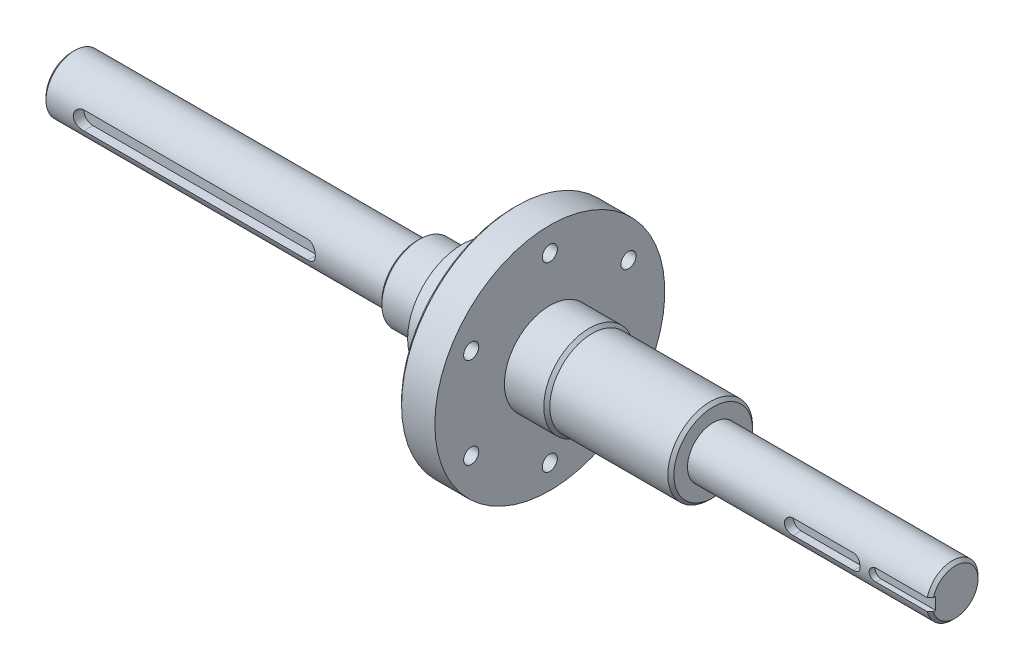
SolidWorks part; units mm, degrees
other "Element opisowy1"
other "Folder spoin"
other "Ścieg spoiny1"
material "40HMT"
ref_plane "Płaszczyzna przednia" through (0, 0, 0) normal (0, 0, 1) x (1, 0, 0)
ref_plane "Płaszczyzna górna" through (0, 0, 0) normal (0, 1, 0) x (1, 0, 0)
ref_plane "Płaszczyzna prawa" through (0, 0, 0) normal (1, 0, 0) x (0, 0, -1)
sketch "Szkic1" plane through (0, 0, 0) normal (0, 0, 1) x (1, 0, 0)
  line L0 (0, 0) -> (292, 0) construction
  line L1 (0, 0) -> (0, 9.5)
  line L2 (0, 9.5) -> (114, 9.5)
  line L3 (114, 9.5) -> (114, 12.5)
  line L4 (114, 12.5) -> (129, 12.5)
  line L5 (129, 12.5) -> (129, 18)
  line L6 (146, 38) -> (158, 38) construction
  line L7 (158, 38) -> (158, 15) construction
  line L8 (158, 15) -> (172, 15)
  line L9 (129, 18) -> (146, 18)
  line L10 (146, 18) -> (146, 38) construction
  line L11 (212, 14) -> (212, 8.5)
  line L12 (212, 8.5) -> (292, 8.5)
  line L13 (146, 18) -> (146, 15)
  line L14 (146, 15) -> (158, 15)
  line L15 (292, 8.5) -> (292, 0)
  line L16 (0, 0) -> (292, 0)
  line L17 (212, 14) -> (172, 14)
  line L18 (172, 14) -> (172, 15)
  dimension "D1" = 19
  dimension "D2" = 114
  dimension "D3" = 25
  dimension "D4" = 38
  dimension "D5" = 36
  dimension "D6" = 129
  dimension "D7" = 30
  dimension "D8" = 66
  dimension "D9" = 12
  dimension "D10" = 29
  dimension "D11" = 17
  dimension "D12" = 80
  dimension "D13" = 14
  dimension "D14" = 1
revolve "Obrót1" add sketch "Szkic1" angle 360 about L16
cosmetic thread "Oznaczenie gwintu1" parameters "D1"=20, "D2"=16
ref_plane "Płaszczyzna1" through (0, 0, 9.5) normal (0, 0, 1) x (1, 0, 0)
sketch "Szkic2" plane through (0, 0, 9.5) normal (0, 0, 1) x (1, 0, 0)
  line L0 (13, 0) -> (87, 0) construction
  line L1 (13, 3) -> (87, 3)
  line L2 (13, -3) -> (87, -3)
  line L8 (0, 9.5) -> (0, -9.5) construction
  arc A0 (13, 3) -> (13, -3) centre (13, 0) ccw
  arc A1 (87, -3) -> (87, 3) centre (87, 0) ccw
  point P3 (50, 0)
  dimension "D2" = 90
  dimension "D3" = 10
  dimension "D1" = 6
extrude "Wytnij-wyciągnięcie1" cut sketch "Szkic2" against normal blind 3.5
hole_wizard "Otwór gwintowany M61" positions "Szkic3" profile "Szkic5" tap size "M6" standard "DIN"
sketch "Szkic3" plane through (0, 0, 0) normal (-1, 0, 0) x (0, 0, 1)
  point P0 (0, 0)
sketch "Szkic5" plane through (0, 0, 0) normal (0, 1, 0) x (0, 0, 1)
  line L0 (0, 0) -> (0, 18.5022)
  line L1 (0, 18.5022) -> (2.5, 17)
  line L2 (2.5, 17) -> (2.5, 0)
  line L5 (2.5, 0) -> (0, 0)
  line L10 (0, 18.5022) -> (-2.5, 17) construction
  line L11 (0, -6.35) -> (0, 107.95) construction
  dimension "Średnica wiertła gwintu" = 5
  dimension "Głębokość otworu gwintowanego" = 17
  dimension "Kąt wiertła" = 118
cosmetic thread "Gwint otworu1" parameters "D1"=12, "D2"=6
chamfer "Sfazowanie1" distance 1 angle 45 1 edges at (0, 0, 9.5)
sketch "Szkic6" plane through (0, 0, 0) normal (0, 0, 1) x (1, 0, 0)
  line L0 (0, 0) -> (292, 0) construction
  line L2 (146, 38) -> (158, 38)
  line L3 (146, 38) -> (146, 15)
  line L4 (146, 15) -> (158, 15)
  line L5 (158, 38) -> (158, 15)
revolve "Obrót2" add sketch "Szkic6" angle 360 about L0
hole_wizard "Otwór gwintowany M62" positions "Szkic7" profile "Szkic8" tap size "M6" standard "DIN" end condition up to next
sketch "Szkic7" plane through (158, 0, 0) normal (1, 0, 0) x (0, 0, -1)
  line L0 (0, 0) -> (0, 30) construction
  point P0 (0, 30)
  dimension "D1" = 30
sketch "Szkic8" plane through (158, 30, 0) normal (0, 1, 0) x (0, 0, -1)
  line L0 (0, 0) -> (0, 12.001)
  line L1 (0, 12.001) -> (2.5, 12.001)
  line L2 (2.5, 12.001) -> (2.5, 0)
  line L5 (2.5, 0) -> (0, 0)
  line L11 (0, -6.35) -> (0, 107.95) construction
  dimension "Średnica otworu gwintowanego na wylot" = 5
  dimension "Głębokość otworu gwintowanego na wylot" = 12.001
cosmetic thread "Gwint otworu2" parameters "D2"=6
pattern_circular "Szyk kołowy1" count 6 over 360 about axis through (0, 0, 0) along (-1, 0, 0) of "Otwór gwintowany M62"
ref_plane "Płaszczyzna2" through (0, 0, 8.5) normal (0, 0, 1) x (1, 0, 0)
sketch "Szkic9" plane through (0, 0, 8.5) normal (0, 0, 1) x (1, 0, 0)
  line L0 (246.5, 0) -> (266.5, 0) construction
  line L1 (246.5, 2.5) -> (266.5, 2.5)
  line L2 (246.5, -2.5) -> (266.5, -2.5)
  line L10 (212, -8.5) -> (212, 8.5) construction
  arc A0 (246.5, 2.5) -> (246.5, -2.5) centre (246.5, 0) ccw
  arc A1 (266.5, -2.5) -> (266.5, 2.5) centre (266.5, 0) ccw
  point P3 (256.5, 0)
  dimension "D1" = 32
  dimension "D3" = 25
  dimension "D2" = 5
extrude "Wytnij-wyciągnięcie2" cut sketch "Szkic9" against normal blind 3
sketch "Szkic10" plane through (292, 0, 0) normal (1, 0, 0) x (0, 0, -1)
  line L1 (-8.5, -2) -> (-8.5, 2)
  line L2 (-8.5, -2) -> (-6.5, -2)
  line L3 (-6.5, -2) -> (-6.5, 2)
  line L4 (-8.5, 2) -> (-6.5, 2)
  circle A0 centre (0, 0) radius 8.5 construction
  point P4 (-6.5, 0)
  dimension "D1" = 4
  dimension "D2" = 6.5
extrude "Wytnij-wyciągnięcie3" cut sketch "Szkic10" against normal blind 20
fillet "Zaokrąglenie1" 2 edges at (272, 2, 7.3807) (272, -2, 7.3807) type full round first side face at (282, 2, 7.3807) second side face at (282, -2, 7.3807) middle face at (272, 0, 7.4403)
chamfer "Sfazowanie2" distance 1 angle 45 1 edges at (292, 0, -8.5)
chamfer "Sfazowanie3" distance 1 angle 45 1 edges at (146, 0, 38)
chamfer "Sfazowanie4" distance 1 angle 45 1 edges at (212, 0, 14)
chamfer "Sfazowanie5" distance 1 angle 45 1 edges at (114, 0, 12.5)
chamfer "Sfazowanie6" distance 1 angle 45 1 edges at (172, 0, 15)
